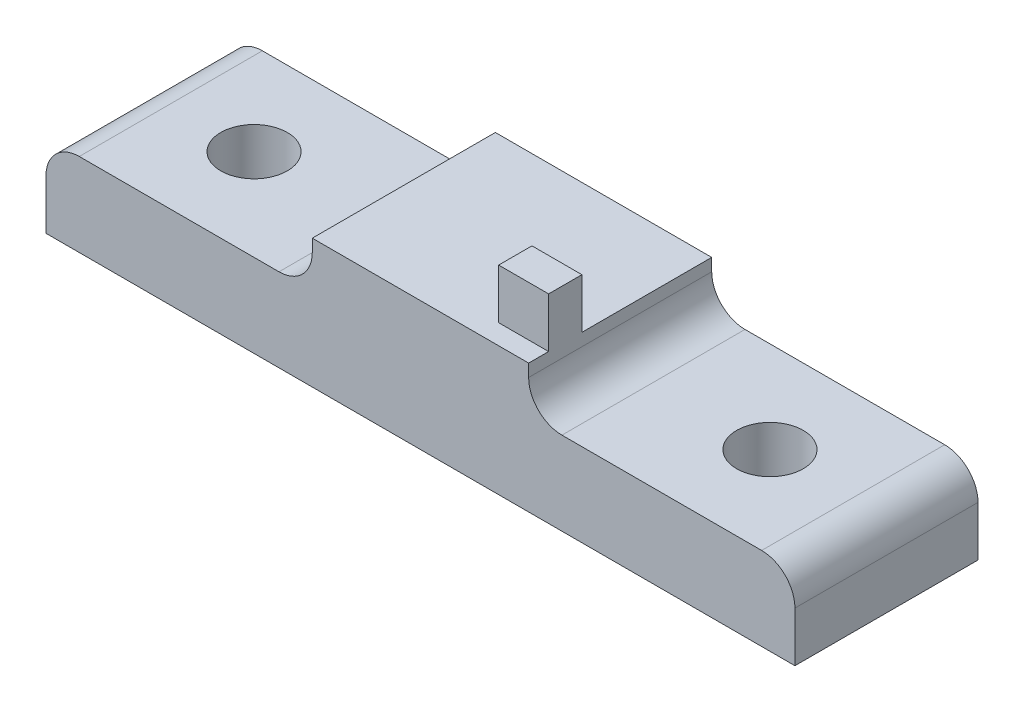
SolidWorks part; units mm, degrees
ref_plane "Front Plane" through (0, 0, 0) normal (0, 0, 1) x (1, 0, 0)
ref_plane "Top Plane" through (0, 0, 0) normal (0, 1, 0) x (1, 0, 0)
ref_plane "Right Plane" through (0, 0, 0) normal (1, 0, 0) x (0, 0, -1)
sketch "Sketch1" plane through (0, 0, 0) normal (0, 0, 1) x (1, 0, 0)
  line L1 (-5.5, -8.425) -> (5.5, -8.425)
  line L2 (-6.5, -7.425) -> (-6.5, 7.425)
  line L3 (-5.5, 8.425) -> (5.5, 8.425)
  line L4 (6.5, -7.425) -> (6.5, 7.425)
  line L5 (-6.5, -8.425) -> (6.5, 8.425) construction
  line L6 (-6.5, 8.425) -> (6.5, -8.425) construction
  arc A0 (-6.5, 7.425) -> (-5.5, 8.425) centre (-5.5, 7.425) cw
  arc A1 (6.5, 7.425) -> (5.5, 8.425) centre (5.5, 7.425) ccw
  arc A2 (-5.5, -8.425) -> (-6.5, -7.425) centre (-5.5, -7.425) cw
  arc A3 (6.5, -7.425) -> (5.5, -8.425) centre (5.5, -7.425) cw
  point P0 (0, 0)
  dimension "D3" = 1
  dimension "D4" = 1
  dimension "D5" = 1
  dimension "D6" = 1
  dimension "D1" = 13
  dimension "D2" = 16.85
extrude "Boss-Extrude1" add sketch "Sketch1" along normal blind 2
sketch "Sketch2" plane through (0, 0, 2) normal (0, 0, 1) x (1, 0, 0)
  line L0 (5.5, 8.425) -> (-5.5, 8.425) construction
  line L2 (-6.5, 7.425) -> (-6.5, -7.425) construction
  circle A0 centre (0, 6.75) radius 1
  circle A1 centre (0, -2) radius 1
  dimension "D1" = 2
  dimension "D2" = 2
  dimension "D3" = 1.675
  dimension "D4" = 8.75
  dimension "D5" = 6.5
  dimension "D6" = 6.5
extrude "Cut-Extrude1" cut sketch "Sketch2" against normal through all
sketch "Sketch3" plane through (0, 0, 2) normal (0, 0, 1) x (1, 0, 0)
  line L0 (0, 2.875) -> (0, 1.875) construction
  line L1 (1.8, 2.875) -> (1.8, 1.875)
  line L2 (-1.8, 2.875) -> (-1.8, 1.875)
  arc A0 (1.8, 2.875) -> (-1.8, 2.875) centre (0, 2.875) ccw
  arc A1 (-1.8, 1.875) -> (1.8, 1.875) centre (0, 1.875) ccw
  circle A2 centre (0, 6.75) radius 1 construction
  point P3 (0, 2.375)
  dimension "D2" = 1
  dimension "D1" = 3.6
  dimension "D3" = 3.875
extrude "Cut-Extrude2" cut sketch "Sketch3" against normal through all
sketch "Sketch4" plane through (0, 0, 0) normal (0, 0, -1) x (-1, 0, 0)
  line L1 (-6.5, -7.425) -> (-6.5, 7.425) construction
  line L2 (-6.5, -3.675) -> (6.5, -3.675)
  line L3 (-6.5, -3.675) -> (-6.5, -8.425)
  line L4 (-6.5, -8.425) -> (6.5, -8.425)
  line L7 (6.5, -3.675) -> (6.5, -8.425)
  line L8 (5.5, -8.425) -> (-5.5, -8.425) construction
  line L9 (6.5, 7.425) -> (6.5, -7.425) construction
  dimension "D1" = 4.75
extrude "Boss-Extrude3" add sketch "Sketch4" along normal blind 15 and the other way up to surface (2 mm away) other way up to face at (0, 2.375, 2)
sketch "Sketch6" plane through (6.5, 0, 0) normal (1, 0, 0) x (0, 0, -1)
  line L1 (15, -8.425) -> (4, -8.425)
  line L2 (15, -8.425) -> (15, -6.425)
  line L3 (15, -6.425) -> (4, -6.425)
  line L4 (4, -8.425) -> (4, -6.425)
  dimension "D1" = 2
  dimension "D2" = 11
extrude "Boss-Extrude4" add sketch "Sketch6" along normal blind 16
sketch "Sketch7" plane through (-6.5, 0, 0) normal (-1, 0, 0) x (0, 0, 1)
  line L1 (-15, -8.425) -> (-4, -8.425)
  line L2 (-15, -8.425) -> (-15, -6.425)
  line L3 (-15, -6.425) -> (-4, -6.425)
  line L4 (-4, -8.425) -> (-4, -6.425)
  dimension "D1" = 2
  dimension "D2" = 11
extrude "Boss-Extrude5" add sketch "Sketch7" along normal blind 16
sketch "Sketch8" plane through (0, -6.425, 0) normal (0, 1, 0) x (1, 0, 0)
  line L0 (22.5, 15) -> (22.5, 4) construction
  line L1 (22.5, 15) -> (6.5, 15) construction
  line L2 (-22.5, 4) -> (-22.5, 15) construction
  line L3 (-22.5, 15) -> (-6.5, 15) construction
  circle A0 centre (15.5, 9.5) radius 2
  circle A1 centre (-15.5, 9.5) radius 2
  dimension "D1" = 4
  dimension "D2" = 7
  dimension "D3" = 5.5
  dimension "D4" = 4
  dimension "D5" = 7
  dimension "D6" = 5.5
extrude "Cut-Extrude3" cut sketch "Sketch8" against normal through all
fillet "Fillet5" radius 2 1 edges at (22.5, -6.425, -9.5)
fillet "Fillet6" radius 2 1 edges at (-22.5, -6.425, -9.5)
fillet "Fillet7" radius 2 1 edges at (6.5, -6.425, -9.5)
fillet "Fillet8" radius 2 1 edges at (-6.5, -6.425, -9.5)
sketch "Sketch10" plane through (6.5, 0, 0) normal (1, 0, 0) x (0, 0, -1)
  line L1 (0, -3.675) -> (-2, -3.675)
  line L2 (0, -3.675) -> (0, 13.2643)
  line L3 (0, 13.2643) -> (-2, 13.2643)
  line L4 (-2, -3.675) -> (-2, 13.2643)
extrude "Cut-Extrude4" cut sketch "Sketch10" against normal through all
sketch "Sketch11" plane through (0, -3.675, 0) normal (0, 1, 0) x (1, 0, 0)
  line L0 (6.5, -2) -> (6.5, 15) construction
  line L1 (-6.5, -2) -> (6.5, -2)
  line L2 (-6.5, -2) -> (-6.5, 4)
  line L3 (-6.5, 4) -> (6.5, 4)
  line L4 (6.5, -2) -> (6.5, 4)
  dimension "D1" = 6
extrude "Cut-Extrude5" cut sketch "Sketch11" against normal through all
sketch "Sketch12" plane through (0, -3.675, 0) normal (0, 1, 0) x (1, 0, 0)
  line L0 (6.5, 4) -> (6.5, 15) construction
  line L1 (6.5, 7.2) -> (3.5, 7.2)
  line L2 (6.5, 7.2) -> (6.5, 5.2)
  line L3 (6.5, 5.2) -> (3.5, 5.2)
  line L4 (3.5, 7.2) -> (3.5, 5.2)
  line L6 (6.5, 4) -> (-6.5, 4) construction
  dimension "D1" = 1.2
  dimension "D2" = 2
  dimension "D3" = 3
extrude "Boss-Extrude6" add sketch "Sketch12" along normal blind 3
sketch "Sketch13" plane through (0, -8.425, 0) normal (0, -1, 0) x (1, 0, 0)
  line L1 (-22.5, -4) -> (22.5, -4)
  line L2 (-22.5, -4) -> (-22.5, -15)
  line L3 (-22.5, -15) -> (22.5, -15)
  line L4 (22.5, -4) -> (22.5, -15)
  circle A0 centre (-15.5, -9.5) radius 2
  circle A1 centre (15.5, -9.5) radius 2
extrude "Boss-Extrude7" add sketch "Sketch13" along normal blind 3
